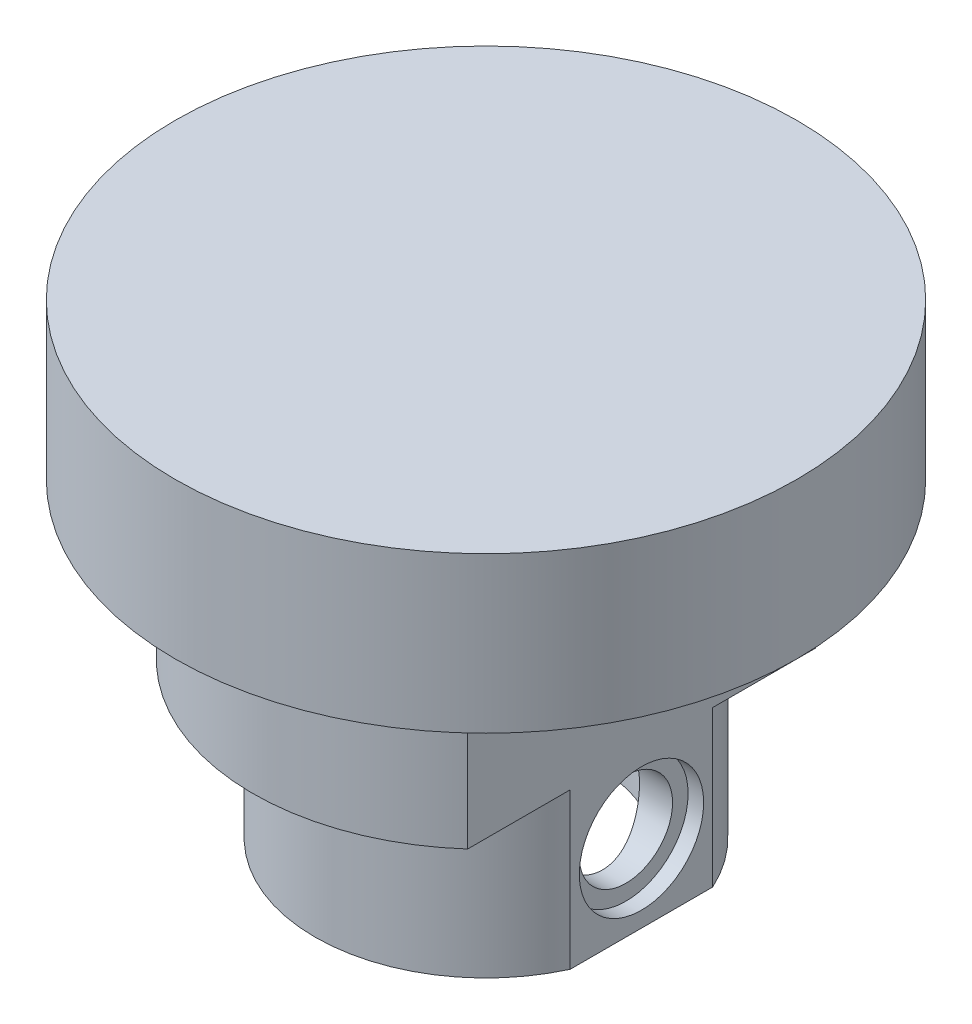
SolidWorks part; units mm, degrees
ref_plane "Front Plane" through (0, 0, 0) normal (0, 0, 1) x (1, 0, 0)
ref_plane "Top Plane" through (0, 0, 0) normal (0, 1, 0) x (1, 0, 0)
ref_plane "Right Plane" through (0, 0, 0) normal (1, 0, 0) x (0, 0, -1)
sketch "Sketch1" plane through (0, 0, 0) normal (0, 1, 0) x (1, 0, 0)
  circle A0 centre (0, 0) radius 20
  dimension "D1" = 40
extrude "Stock" add sketch "Sketch1" against normal blind 20
sketch "Sketch2" plane through (0, 0, 0) normal (0, 1, 0) x (1, 0, 0)
  circle A0 centre (0, 0) radius 15
  dimension "D1" = 30
extrude "Cut-Extrude1" cut sketch "Sketch2" against normal up to surface (20 mm away) from offset 10 flip side to cut up to face at (0, -20, 20) offset against normal yes
sketch "Sketch4" plane through (0, 0, 0) normal (0, 1, 0) x (1, 0, 0)
  circle A0 centre (0, 0) radius 11
  dimension "D1" = 22
extrude "Boss-Extrude2" add sketch "Sketch4" against normal blind 10 from surface starting at face at (0, -20, 15)
sketch "Sketch3" plane through (0, 0, 0) normal (0, 1, 0) x (1, 0, 0)
  line L0 (10, -11.1803) -> (10, 11.1803)
  circle A0 centre (0, 0) radius 15 construction
  dimension "D1" = 10
extrude "MainKey" cut sketch "Sketch3" against normal through all from surface thin starting at face at (0, -10, 20) thin type one direction wall 10
sketch "Sketch5" plane through (0, 0, 0) normal (0, 1, 0) x (1, 0, 0)
  circle A0 centre (0, 0) radius 7.5
  dimension "D1" = 15
extrude "CentreBore" cut sketch "Sketch5" along normal offset from surface (25 mm away) 5 from surface up to face at (0, 0, 20) starting at face at (-0.5, -30, 0)
sketch "Sketch6" plane through (10, 0, 0) normal (1, 0, 0) x (0, 0, -1)
  line L0 (-11.1803, -10) -> (11.1803, -10) construction
  circle A0 centre (0, -25) radius 3
  dimension "D1" = 6
  dimension "D2" = 15
extrude "Holes" cut sketch "Sketch6" against normal offset from surface (23.6748 mm away) 1 up to face at (-2.5, -15, 0)
sketch "Sketch7" plane through (10, 0, 0) normal (1, 0, 0) x (0, 0, -1)
  circle A0 centre (0, -25) radius 4
  dimension "D1" = 8
extrude "Cut-Extrude4" cut sketch "Sketch7" against normal blind 1
